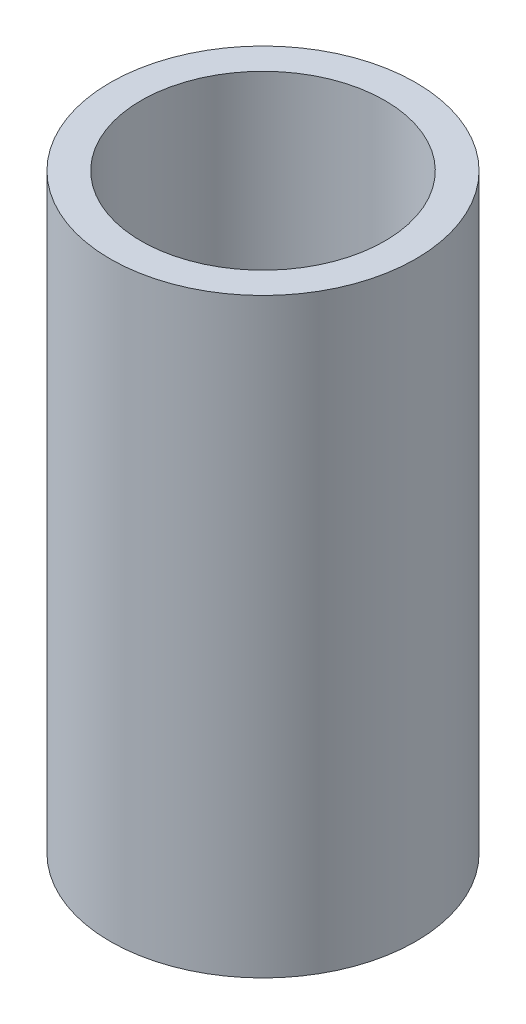
SolidWorks part; units mm, degrees
ref_plane "Front Plane" through (0, 0, 0) normal (0, 0, 1) x (1, 0, 0)
ref_plane "Top Plane" through (0, 0, 0) normal (0, 1, 0) x (1, 0, 0)
ref_plane "Right Plane" through (0, 0, 0) normal (1, 0, 0) x (0, 0, -1)
sketch "Sketch1" plane through (0, 0, 0) normal (0, 1, 0) x (1, 0, 0)
  circle A0 centre (0, 0) radius 27.5
  dimension "SLEEVE_OD" = 55
extrude "Boss-Extrude1" add sketch "Sketch1" along normal blind 106.3864
sketch "Sketch2" plane through (0, 0, 0) normal (0, 1, 0) x (1, 0, 0)
  circle A0 centre (0, 0) radius 21.9295
  dimension "BORE_D" = 43.8589
extrude "Cut-Extrude1" cut sketch "Sketch2" along normal through all
chamfer "Chamfer1" distance 3.6934 angle 43.496 rebuild error yes
